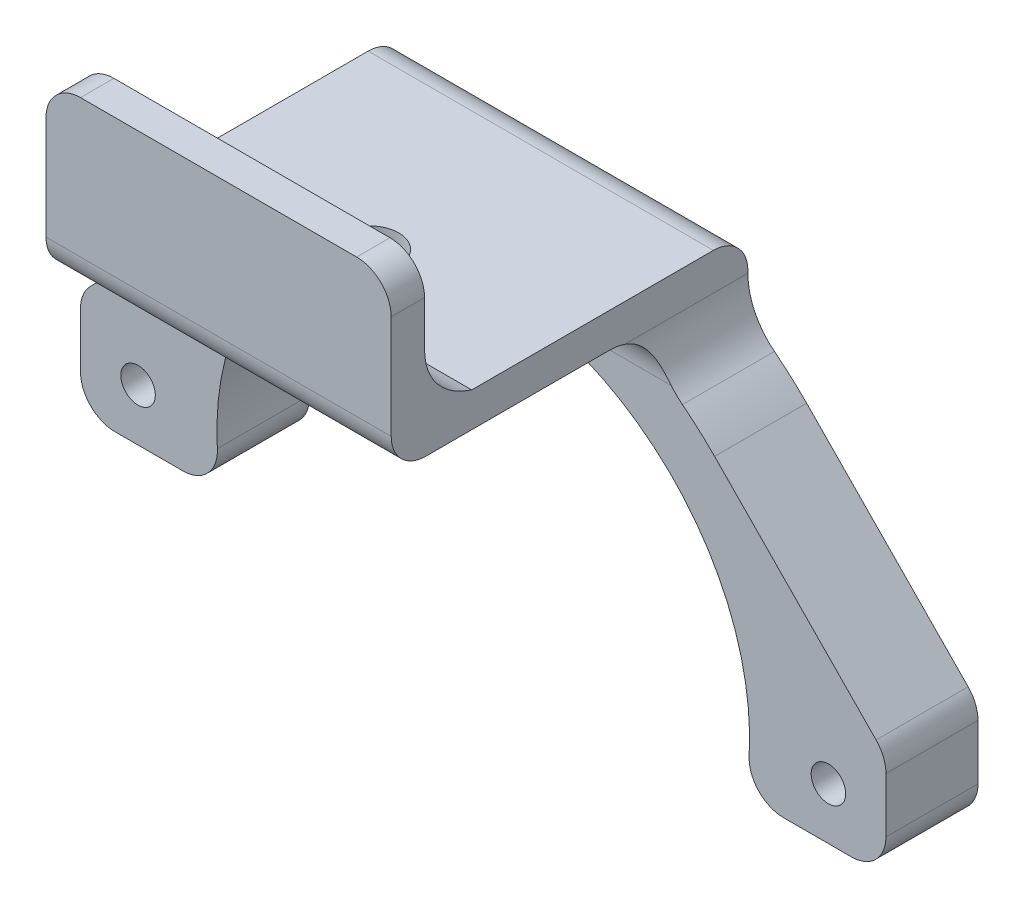
SolidWorks part; units mm, degrees
ref_plane "前视基准面" through (0, 0, 0) normal (0, 0, 1) x (1, 0, 0)
ref_plane "上视基准面" through (0, 0, 0) normal (0, 1, 0) x (1, 0, 0)
ref_plane "右视基准面" through (0, 0, 0) normal (1, 0, 0) x (0, 0, -1)
other "Configuration Table"
sketch "草图1" plane through (0, 0, 0) normal (0, 0, 1) x (1, 0, 0)
  line L0 (22.5555, 4.5) -> (75, 4.5) construction
  line L1 (-75, -4.5) -> (-22.5555, -4.5) construction
  line L2 (-75, -4.5) -> (-75, 4.5) construction
  line L3 (-75, 4.5) -> (-22.5555, 4.5) construction
  line L4 (75, -4.5) -> (75, 4.5) construction
  line L5 (-75, -4.5) -> (75, 4.5) construction
  line L6 (-75, 4.5) -> (75, -4.5) construction
  line L7 (22.5555, -4.5) -> (75, -4.5) construction
  line L8 (-70, 0) -> (-75, 0) construction
  line L9 (-27.788, -4.5) -> (-35, -4.5)
  line L10 (-35, -4.5) -> (-35, 4.5)
  line L11 (0, 20.75) -> (0, -20.75) construction
  line L12 (-35, 4.5) -> (-20.1078, 19.7003)
  line L13 (27.788, -4.5) -> (35, -4.5)
  line L14 (35, -4.5) -> (35, 4.5)
  line L15 (35, 4.5) -> (20.1078, 19.7003)
  line L16 (-27.788, -4.5) -> (-22.5555, -4.5)
  line L17 (22.5555, -4.5) -> (27.788, -4.5)
  circle A0 centre (0, 20.75) radius 1.5 construction
  circle A1 centre (14.6725, 14.6725) radius 1.5 construction
  circle A2 centre (20.75, 0) radius 1.5 construction
  circle A3 centre (14.6725, -14.6725) radius 1.5 construction
  circle A4 centre (0, -20.75) radius 1.5 construction
  circle A5 centre (-14.6725, -14.6725) radius 1.5 construction
  circle A6 centre (-20.75, 0) radius 1.5 construction
  circle A7 centre (-14.6725, 14.6725) radius 1.5 construction
  circle A8 centre (0, 0) radius 17.5 construction
  circle A9 centre (0, 0) radius 23 construction
  arc A10 (-22.5555, 4.5) -> (22.5555, 4.5) centre (0, 0) cw construction
  arc A11 (22.5555, -4.5) -> (-22.5555, -4.5) centre (0, 0) cw construction
  circle A12 centre (-70, 0) radius 1.5 construction
  circle A13 centre (-50, 0) radius 1.5 construction
  circle A14 centre (-30, 0) radius 1.5
  circle A15 centre (-10, 0) radius 1.5 construction
  circle A17 centre (30, 0) radius 1.5
  circle A18 centre (50, 0) radius 1.5 construction
  circle A19 centre (70, 0) radius 1.5 construction
  circle A21 centre (10, 0) radius 1.5 [skipped]
  circle A22 centre (90, 0) radius 1.5 [skipped]
  circle A23 centre (0, 0) radius 23.15
  circle A24 centre (0, 0) radius 28.15
  point P19 (0, 0)
  point P25 (22.5555, 4.5)
  point P26 (22.5555, -4.5)
  point P27 (-22.5555, 4.5)
  point P28 (-22.5555, -4.5)
  dimension "D2" = 3
  dimension "D4" = 35
  dimension "D5" = 46
  dimension "D8" = 3
  dimension "D12" = 46.3
  dimension "D1" = 20.75
  dimension "D3" = 8
  dimension "D6" = 9
  dimension "D7" = 150
  dimension "D9" = 5
  dimension "D11" = 20
  dimension "D14" = 35
  dimension "D13" = 5
  dimension "D10" = 9
extrude "凸台-拉伸1" add sketch "草图1" along normal blind 8 contours A24 L12 L10 L9 A14 | A24 L16 A23 L17 | A24 L13 L14 L15 A17 region at (-26.2109, 8.3183, 0) region at (-30.5148, 3.5496, 0) region at (30.5148, 3.5496, 0)
sketch "草图2" plane through (0, 0, 8) normal (0, 0, 1) x (1, 0, 0)
  line L0 (-15, 28.15) -> (15, 28.15)
  line L1 (-15, 28.15) -> (15, 28.15)
  line L2 (-15, 28.15) -> (-15, 27.15)
  line L3 (15, 28.15) -> (15, 27.15)
  line L4 (-15, 27.15) -> (-7.4364, 27.15)
  line L5 (-15, 27.15) -> (-15, 23.8206)
  line L6 (-35, -4.5) -> (-22.7084, -4.5)
  line L7 (22.7084, -4.5) -> (35, -4.5)
  line L8 (35, -4.5) -> (35, 4.5)
  line L9 (35, 4.5) -> (20.1078, 19.7003)
  line L10 (-20.1078, 19.7003) -> (-35, 4.5)
  line L11 (-35, 4.5) -> (-35, -4.5)
  line L12 (-35, -4.5) -> (-22.7084, -4.5)
  line L13 (22.7084, -4.5) -> (35, -4.5)
  line L14 (35, -4.5) -> (35, 4.5)
  line L15 (35, 4.5) -> (20.1078, 19.7003)
  line L16 (-20.1078, 19.7003) -> (-35, 4.5)
  line L17 (-35, 4.5) -> (-35, -4.5)
  line L18 (15, 27.15) -> (15, 23.8206)
  line L19 (-15, 28.15) -> (15, 28.15)
  line L20 (-15, 28.15) -> (-15, 30.15)
  line L21 (15, 28.15) -> (15, 30.15)
  line L22 (-15, 30.15) -> (15, 30.15)
  line L23 (7.4364, 27.15) -> (15, 27.15)
  arc A2 (22.7084, -4.5) -> (-22.7084, -4.5) centre (0, 0) ccw
  arc A3 (20.1078, 19.7003) -> (-20.1078, 19.7003) centre (0, 0) ccw
  arc A4 (22.7084, -4.5) -> (-22.7084, -4.5) centre (0, 0) ccw
  arc A5 (20.1078, 19.7003) -> (-20.1078, 19.7003) centre (0, 0) ccw
  point P11 (0, 28.15)
  arc M18 (20.1078, 19.7003) -> (-20.1078, 19.7003) centre (0, 0) ccw
  dimension "D2" = 30
  dimension "D3" = 1
  dimension "D4" = 2
  dimension "D1" = 0
extrude "凸台-拉伸2" add sketch "草图2" against normal blind 8 contours L4 L5 M18 | L23 L18 M18 | L23 L3 L0 M18 | L2 L4 L0 M18 | L22 L20 L0 L21 region at (0, 29.15, 8) region at (-9.8351, 27.6993, 8) region at (9.8351, 27.6993, 8) region at (-12.6655, 26.1085, 8) region at (12.6655, 26.1085, 8)
sketch "草图3" plane through (0, 0, 8) normal (0, 0, 1) x (1, 0, 0)
  line L0 (-15, 27.15) -> (15, 27.15)
  line L1 (-15, 23.8206) -> (-15, 30.15) construction
  line L2 (15, 30.15) -> (15, 23.8206) construction
  line L3 (-15, 30.15) -> (15, 30.15) construction
  line L13 (-35, -4.5) -> (-22.7084, -4.5)
  line L14 (22.7084, -4.5) -> (35, -4.5)
  line L15 (35, -4.5) -> (35, 4.5)
  line L16 (35, 4.5) -> (20.1078, 19.7003)
  line L17 (15, 23.8206) -> (15, 30.15)
  line L18 (15, 30.15) -> (-15, 30.15)
  line L19 (-15, 30.15) -> (-15, 23.8206)
  line L20 (-20.1078, 19.7003) -> (-35, 4.5)
  line L21 (-35, 4.5) -> (-35, -4.5)
  line L22 (-35, -4.5) -> (-22.7084, -4.5)
  line L23 (22.7084, -4.5) -> (35, -4.5)
  line L24 (35, -4.5) -> (35, 4.5)
  line L25 (35, 4.5) -> (20.1078, 19.7003)
  line L26 (15, 23.8206) -> (15, 30.15)
  line L27 (15, 30.15) -> (-15, 30.15)
  line L28 (-15, 30.15) -> (-15, 23.8206)
  line L29 (-20.1078, 19.7003) -> (-35, 4.5)
  line L30 (-35, 4.5) -> (-35, -4.5)
  arc A3 (22.7084, -4.5) -> (-22.7084, -4.5) centre (0, 0) ccw
  arc A4 (20.1078, 19.7003) -> (15, 23.8206) centre (0, 0) ccw
  arc A5 (-15, 23.8206) -> (-20.1078, 19.7003) centre (0, 0) ccw
  arc A6 (22.7084, -4.5) -> (-22.7084, -4.5) centre (0, 0) ccw
  arc A7 (20.1078, 19.7003) -> (15, 23.8206) centre (0, 0) ccw
  arc A8 (-15, 23.8206) -> (-20.1078, 19.7003) centre (0, 0) ccw
  line M20 (15, 23.8206) -> (15, 30.15)
  line M21 (15, 30.15) -> (-15, 30.15)
  line M22 (-15, 30.15) -> (-15, 23.8206)
  dimension "D1" = 3
  dimension "D2" = 0
extrude "凸台-拉伸3" add sketch "草图3" along normal blind 20 contours L0 M22 M20 M21 region at (0, 28.65, 8)
sketch "草图4" plane through (0, 30.15, 0) normal (0, 1, 0) x (1, 0, 0)
  line L0 (15, -28) -> (-15, -28) construction
  circle A0 centre (0, -17.85) radius 2.5
  point P4 (-0.689, -13.85)
  dimension "D1" = 5
  dimension "D2" = 10.15
extrude "切除-拉伸1" cut sketch "草图4" against normal through all
sketch "草图5" plane through (-15, 0, 0) normal (-1, 0, 0) x (0, 0, 1)
  line L0 (28.1, 35.6375) -> (28.1, 42.15)
  line L1 (28.1, 42.15) -> (31, 42.15)
  line L2 (31, 42.15) -> (31, 27.15)
  line L3 (31, 27.15) -> (28, 27.15)
  line L6 (8, 23.8206) -> (8, 27.15)
  line L7 (8, 27.15) -> (28, 27.15)
  line L8 (28, 27.15) -> (28, 30.15)
  line L9 (28, 30.15) -> (0, 30.15)
  line L10 (0, 30.15) -> (0, 23.8206)
  line L11 (0, 23.8206) -> (8, 23.8206)
  line L12 (8, 23.8206) -> (8, 27.15)
  line L13 (8, 27.15) -> (28, 27.15)
  line L14 (28, 27.15) -> (28, 30.15)
  line L15 (28, 30.15) -> (0, 30.15)
  line L16 (0, 30.15) -> (0, 23.8206)
  line L17 (0, 23.8206) -> (8, 23.8206)
  spline S1 degree 3 poles (23.7955, 30.1868) (24.3116, 30.3576) (25.434, 30.7723) (27.0352, 32.088) (27.8161, 33.6061) (27.9978, 34.7978) (27.9998, 35.3667) (28, 35.6376) knots 0.000013 0.000013 0.000013 0.000013 0.235515 0.493921 0.752327 0.88153 1 1 1 1 weights 1 1 1 1 1 1 1 1 construction
  spline S2 degree 1 poles (23.8269, 30.0918) (28.1, 35.6375) knots 0 0 1 1 construction
  spline S3 degree 3 poles (23.8269, 30.0918) (23.8713, 30.1065) (23.9419, 30.1301) (24.2203, 30.2253) (24.7363, 30.4157) (25.8056, 30.9363) (27.138, 32.0678) (27.9044, 33.5643) (28.0976, 34.7729) (28.0998, 35.3466) (28.1, 35.6375) knots 0.000013 0.000013 0.000013 0.000013 0.019576 0.032618 0.125011 0.25001 0.500007 0.750003 0.875002 1 1 1 1
  point P14 (24, 30.15)
  line M11 (28, 27.15) -> (28, 30.15)
  line M12 (28, 30.15) -> (0, 30.15)
  dimension "D3" = 3
  dimension "D4" = 15
  dimension "D5" = 4
  dimension "D6" = 2.9
  dimension "D1" = 0
  dimension "D2" = 0.1
extrude "凸台-拉伸4" add sketch "草图5" against normal up to surface (30 mm away) contours S3 L3 L2 L1 L0 M12 M11 region at (-15, 34.2374, 29.2538) up to face at (15, 27.0402, 12)
fillet "圆角1" radius 4 1 edges at (0, 27.15, 8)
fillet "圆角2" radius 6 2 edges at (15, 23.8206, 4.0283) (-15, 23.8206, 4.0283)
fillet "圆角3" radius 3 8 edges at (22.7084, -4.5, 4) (-22.7084, -4.5, 4) (35, -4.5, 4) (-35, -4.5, 4) (0, 27.15, 31) (0, 30.15, 0) (35, 4.5, 4) (-35, 4.5, 4)
fillet "圆角4" radius 3 2 edges at (15, 42.15, 29.55) (-15, 42.15, 29.55)
